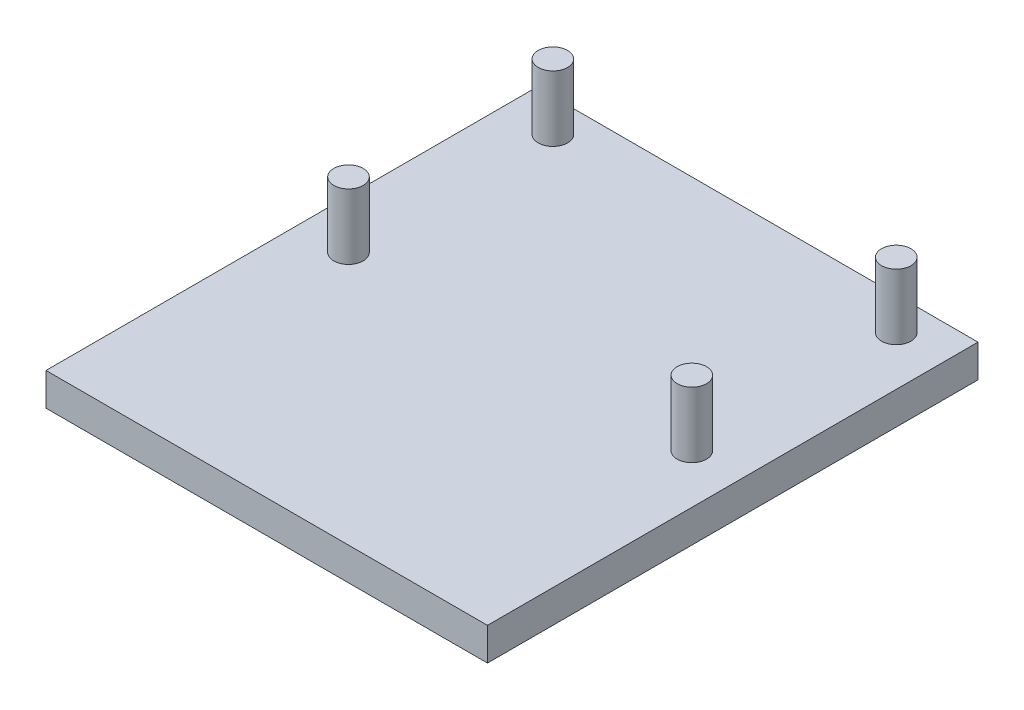
SolidWorks part; units mm, degrees
ref_plane "Front Plane" through (0, 0, 0) normal (0, 0, 1) x (1, 0, 0)
ref_plane "Top Plane" through (0, 0, 0) normal (0, 1, 0) x (1, 0, 0)
ref_plane "Right Plane" through (0, 0, 0) normal (1, 0, 0) x (0, 0, -1)
sketch "Sketch3" plane through (0, 0, 0) normal (0, 1, 0) x (1, 0, 0)
  line L1 (-13.5, 0) -> (13.5, 0)
  line L2 (-13.5, 0) -> (-13.5, -30)
  line L3 (-13.5, -30) -> (13.5, -30)
  line L4 (13.5, 0) -> (13.5, -30)
  point P4 (17.816, -8.8031)
  dimension "D1" = 27
  dimension "D2" = 30
extrude "Boss-Extrude1" add sketch "Sketch3" against normal blind 2
sketch "Sketch2" plane through (0, 0, 0) normal (0, 1, 0) x (1, 0, 0)
  line L0 (0, 0) -> (0, -30) construction
  line L1 (-13.5, -30) -> (13.5, -30) construction
  line L2 (13.5, 0) -> (-13.5, 0) construction
  line L3 (-13.5, 0) -> (-13.5, -30) construction
  circle A0 centre (-10.5, -2) radius 0.9
  circle A1 centre (-10.5, -14.5) radius 0.9
  circle A2 centre (10.5, -14.5) radius 0.9
  circle A3 centre (10.5, -2) radius 0.9
  dimension "D1" = 1.8
  dimension "D2" = 1.8
  dimension "D4" = 10.5
  dimension "D5" = 2
  dimension "D6" = 3
  dimension "D3" = 12.5
extrude "Boss-Extrude2" add sketch "Sketch2" along normal blind 4
